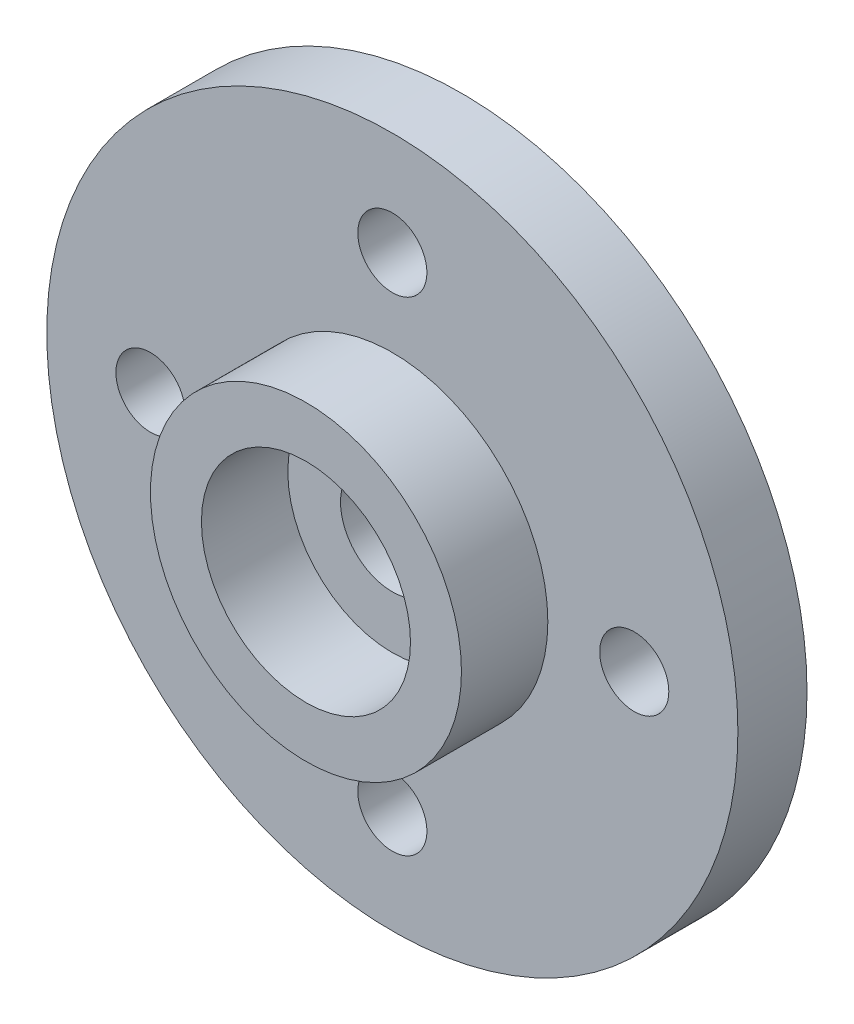
SolidWorks part; units mm, degrees
material "1345 Alloy"
ref_plane "Front Plane" through (0, 0, 0) normal (0, 0, 1) x (1, 0, 0)
ref_plane "Top Plane" through (0, 0, 0) normal (0, 1, 0) x (1, 0, 0)
ref_plane "Right Plane" through (0, 0, 0) normal (1, 0, 0) x (0, 0, -1)
sketch "Sketch1" plane through (0, 0, 0) normal (0, 0, 1) x (1, 0, 0)
  circle A0 centre (0, 0) radius 10
  circle A1 centre (7, 0) radius 1
  circle A2 centre (0, 7) radius 1
  circle A3 centre (0, 0) radius 1.5
  circle A4 centre (0, -7) radius 1
  circle A5 centre (-7, 0) radius 1
  dimension "D1" = 20
  dimension "D2" = 3
  dimension "D3" = 2
  dimension "D4" = 2
  dimension "D5" = 7
  dimension "D6" = 7
extrude "Boss-Extrude1" add sketch "Sketch1" along normal blind 2
sketch "Sketch2" plane through (0, 0, 2) normal (0, 0, 1) x (1, 0, 0)
  circle A0 centre (0, 0) radius 4.5
  circle A1 centre (0, 0) radius 3.025
  dimension "D1" = 9
  dimension "D2" = 6.05
extrude "Boss-Extrude2" add sketch "Sketch2" along normal blind 2.5
ref_axis "Axis1" through (0, 0, 2) along (0, 0, -1)
ref_point "Point1"
